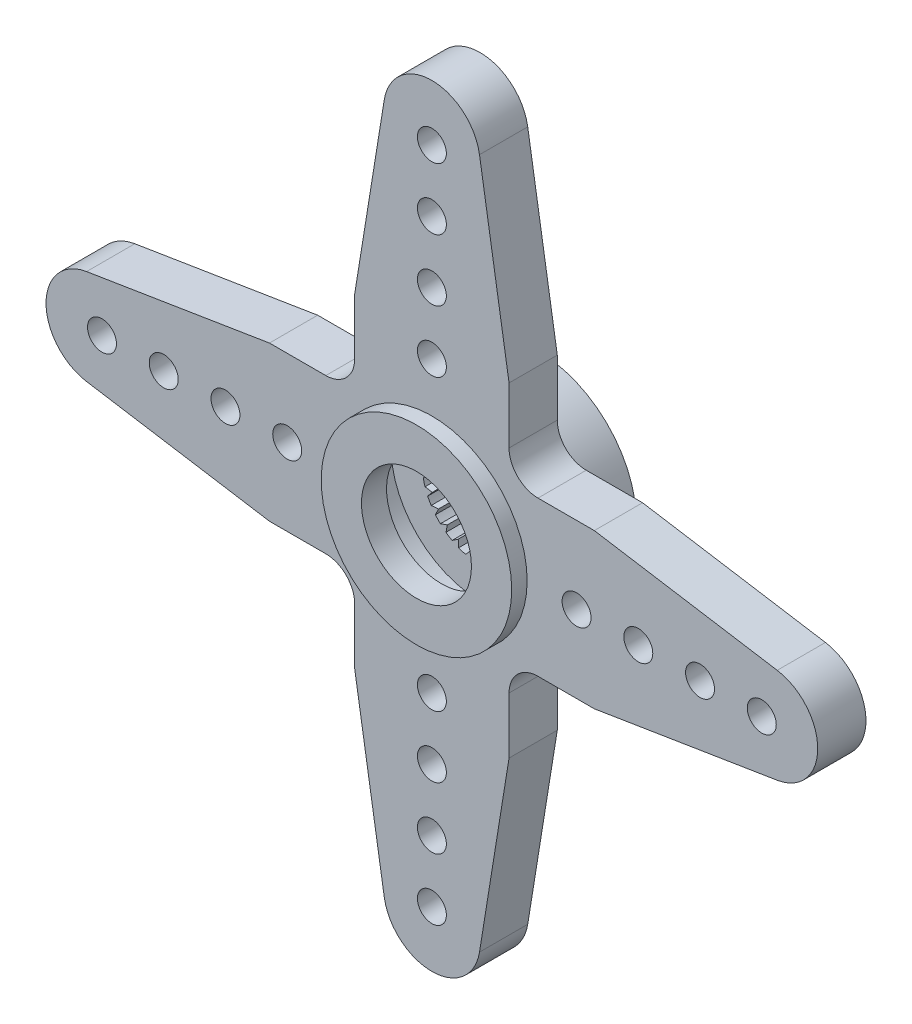
SolidWorks part; units mm, degrees
ref_plane "Front Plane" through (0, 0, 0) normal (0, 0, 1) x (1, 0, 0)
ref_plane "Top Plane" through (0, 0, 0) normal (0, 1, 0) x (1, 0, 0)
ref_plane "Right Plane" through (0, 0, 0) normal (1, 0, 0) x (0, 0, -1)
ref_plane "Plane1" through (0, 0, 2.5) normal (0, 0, 1) x (1, 0, 0)
sketch "Sketch1" plane through (0, 0, 2.5) normal (0, 0, 1) x (1, 0, 0)
  line L0 (4, -8.4192) -> (4, -4)
  line L1 (4, -4) -> (8.4192, -4)
  line L2 (8.4192, -4) -> (17.8989, -2.468)
  line L3 (17.8989, 2.468) -> (8.4192, 4)
  line L4 (8.4192, 4) -> (4, 4)
  line L5 (4, 4) -> (4, 8.4192)
  line L6 (4, 8.4192) -> (2.468, 17.8989)
  line L7 (-2.468, 17.8989) -> (-4, 8.4192)
  line L8 (-4, 8.4192) -> (-4, 4)
  line L9 (-4, 4) -> (-8.4192, 4)
  line L10 (-8.4192, 4) -> (-17.8989, 2.468)
  line L11 (-17.8989, -2.468) -> (-8.4192, -4)
  line L12 (-8.4192, -4) -> (-4, -4)
  line L13 (-4, -4) -> (-4, -8.4192)
  line L14 (-4, -8.4192) -> (-2.468, -17.8989)
  line L15 (2.468, -17.8989) -> (4, -8.4192)
  arc A0 (17.8989, -2.468) -> (17.8989, 2.468) centre (17.5, 0) ccw
  arc A1 (2.468, 17.8989) -> (-2.468, 17.8989) centre (0, 17.5) ccw
  arc A2 (-17.8989, 2.468) -> (-17.8989, -2.468) centre (-17.5, 0) ccw
  arc A3 (-2.468, -17.8989) -> (2.468, -17.8989) centre (0, -17.5) ccw
extrude "Boss-Extrude1" add sketch "Sketch1" against normal blind 2.5
hole_wizard "M8 Clearance Hole1" positions "Sketch3" profile "Sketch2" hole size "M8" standard "ANSI Metric"
sketch "Sketch3" plane through (0, 0, 2.5) normal (0, 0, 1) x (1, 0, 0)
  point P0 (0, 0)
sketch "Sketch2" plane through (0, 0, 2.5) normal (1, 0, 0) x (0, -1, 0)
  line L0 (0, 0) -> (0, 2.5)
  line L1 (0, 2.5) -> (4.625, 2.5)
  line L2 (4.625, 2.5) -> (4.625, 0)
  line L5 (4.625, 0) -> (0, 0)
  line L11 (0, -6.35) -> (0, 107.95) construction
  dimension "Thru Hole Dia." = 9.25
  dimension "Thru Hole Depth" = 2.5
ref_plane "Plane2" through (0, 0, 2) normal (0, 0, -1) x (-1, 0, 0)
sketch "Sketch4" plane through (0, 0, 2) normal (0, 0, -1) x (-1, 0, 0)
  circle A0 centre (0, 0) radius 4.938
extrude "Boss-Extrude2" add sketch "Sketch4" against normal blind 1.3
sketch "Sketch5" plane through (0, 0, 0) normal (0, 0, 1) x (1, 0, 0)
  circle A0 centre (0, 0) radius 5.0996
extrude "Boss-Extrude3" add sketch "Sketch5" against normal blind 3
sketch "Sketch6" plane through (0, 0, -3) normal (0, 0, -1) x (-1, 0, 0)
  line L0 (-2.9946, 0.1807) -> (-2.6675, 0)
  line L1 (-2.6675, 0) -> (-2.9936, -0.1964)
  line L2 (-2.9454, -0.5697) -> (-2.5837, -0.6634)
  line L3 (-2.5837, -0.6634) -> (-2.8507, -0.9347)
  line L4 (-2.7112, -1.2843) -> (-2.3375, -1.2851)
  line L5 (-2.3375, -1.2851) -> (-2.5287, -1.6143)
  line L6 (-2.3066, -1.9182) -> (-1.9445, -1.826)
  line L7 (-1.9445, -1.826) -> (-2.0478, -2.1924)
  line L8 (-1.7571, -2.4316) -> (-1.4293, -2.2522)
  line L9 (-1.4293, -2.2522) -> (-1.4382, -2.6328)
  line L10 (-1.0972, -2.7922) -> (-0.8243, -2.5369)
  line L11 (-0.8243, -2.5369) -> (-0.7383, -2.9077)
  line L12 (-0.3683, -2.9773) -> (-0.1675, -2.6622)
  line L13 (-0.1675, -2.6622) -> (0.0081, -3)
  line L14 (0.3837, -2.9754) -> (0.4998, -2.6202)
  line L15 (0.4998, -2.6202) -> (0.7539, -2.9037)
  line L16 (1.1115, -2.7865) -> (1.1358, -2.4136)
  line L17 (1.1358, -2.4136) -> (1.4523, -2.625)
  line L18 (1.7696, -2.4225) -> (1.7003, -2.0553)
  line L19 (1.7003, -2.0553) -> (2.0595, -2.1814)
  line L20 (2.3164, -1.9063) -> (2.158, -1.5679)
  line L21 (2.158, -1.5679) -> (2.5373, -1.6007)
  line L22 (2.7178, -1.2704) -> (2.4802, -0.982)
  line L23 (2.4802, -0.982) -> (2.8556, -0.9194)
  line L24 (2.9483, -0.5546) -> (2.6464, -0.3343)
  line L25 (2.6464, -0.3343) -> (2.9946, -0.1803)
  line L26 (2.9936, 0.1961) -> (2.6464, 0.3343)
  line L27 (2.6464, 0.3343) -> (2.9453, 0.5701)
  line L28 (2.8508, 0.9344) -> (2.4802, 0.982)
  line L29 (2.4802, 0.982) -> (2.711, 1.2846)
  line L30 (2.5288, 1.614) -> (2.158, 1.5679)
  line L31 (2.158, 1.5679) -> (2.3064, 1.9185)
  line L32 (2.048, 2.1922) -> (1.7003, 2.0553)
  line L33 (1.7003, 2.0553) -> (1.7568, 2.4318)
  line L34 (1.4385, 2.6326) -> (1.1358, 2.4136)
  line L35 (1.1358, 2.4136) -> (1.0969, 2.7923)
  line L36 (0.7386, 2.9077) -> (0.4998, 2.6202)
  line L37 (0.4998, 2.6202) -> (0.368, 2.9773)
  line L38 (-0.0077, 3) -> (-0.1675, 2.6622)
  line L39 (-0.1675, 2.6622) -> (-0.384, 2.9753)
  line L40 (-0.7535, 2.9038) -> (-0.8243, 2.5369)
  line L41 (-0.8243, 2.5369) -> (-1.1119, 2.7864)
  line L42 (-1.452, 2.6252) -> (-1.4293, 2.2522)
  line L43 (-1.4293, 2.2522) -> (-1.7699, 2.4223)
  line L44 (-2.0593, 2.1816) -> (-1.9445, 1.826)
  line L45 (-1.9445, 1.826) -> (-2.3167, 1.9061)
  line L46 (-2.5371, 1.601) -> (-2.3375, 1.2851)
  line L47 (-2.3375, 1.2851) -> (-2.7179, 1.27)
  line L48 (-2.8555, 0.9197) -> (-2.5837, 0.6634)
  line L49 (-2.5837, 0.6634) -> (-2.9484, 0.5542)
  arc A0 (-2.9936, -0.1964) -> (-2.9454, -0.5697) centre (0, 0) ccw
  arc A1 (-2.8507, -0.9347) -> (-2.7112, -1.2843) centre (0, 0) ccw
  arc A2 (-2.5287, -1.6143) -> (-2.3066, -1.9182) centre (0, 0) ccw
  arc A3 (-2.0478, -2.1924) -> (-1.7571, -2.4316) centre (0, 0) ccw
  arc A4 (-1.4382, -2.6328) -> (-1.0972, -2.7922) centre (0, 0) ccw
  arc A5 (-0.7383, -2.9077) -> (-0.3683, -2.9773) centre (0, 0) ccw
  arc A6 (0.0081, -3) -> (0.3837, -2.9754) centre (0, 0) ccw
  arc A7 (0.7539, -2.9037) -> (1.1115, -2.7865) centre (0, 0) ccw
  arc A8 (1.4523, -2.625) -> (1.7696, -2.4225) centre (0, 0) ccw
  arc A9 (2.0595, -2.1814) -> (2.3164, -1.9063) centre (0, 0) ccw
  arc A10 (2.5373, -1.6007) -> (2.7178, -1.2704) centre (0, 0) ccw
  arc A11 (2.8556, -0.9194) -> (2.9483, -0.5546) centre (0, 0) ccw
  arc A12 (2.9946, -0.1803) -> (2.9936, 0.1961) centre (0, 0) ccw
  arc A13 (2.9453, 0.5701) -> (2.8508, 0.9344) centre (0, 0) ccw
  arc A14 (2.711, 1.2846) -> (2.5288, 1.614) centre (0, 0) ccw
  arc A15 (2.3064, 1.9185) -> (2.048, 2.1922) centre (0, 0) ccw
  arc A16 (1.7568, 2.4318) -> (1.4385, 2.6326) centre (0, 0) ccw
  arc A17 (1.0969, 2.7923) -> (0.7386, 2.9077) centre (0, 0) ccw
  arc A18 (0.368, 2.9773) -> (-0.0077, 3) centre (0, 0) ccw
  arc A19 (-0.384, 2.9753) -> (-0.7535, 2.9038) centre (0, 0) ccw
  arc A20 (-1.1119, 2.7864) -> (-1.452, 2.6252) centre (0, 0) ccw
  arc A21 (-1.7699, 2.4223) -> (-2.0593, 2.1816) centre (0, 0) ccw
  arc A22 (-2.3167, 1.9061) -> (-2.5371, 1.601) centre (0, 0) ccw
  arc A23 (-2.7179, 1.27) -> (-2.8555, 0.9197) centre (0, 0) ccw
  arc A24 (-2.9484, 0.5542) -> (-2.9946, 0.1807) centre (0, 0) ccw
extrude "Cut-Extrude1" cut sketch "Sketch6" against normal blind 3.6
hole_wizard "Ø1.5 (1.5) Diameter Hole1" positions "Sketch8" profile "Sketch7" hole size "Ø1.5" standard "ANSI Metric"
sketch "Sketch8" plane through (0, 0, 0) normal (0, 0, -1) x (-1, 0, 0)
  point P0 (0, 17.1)
  point P1 (0, 13.9)
  point P2 (0, 10.7)
  point P3 (0, 7.5)
  point P4 (17.1, 0)
  point P5 (13.9, 0)
  point P6 (10.7, 0)
  point P7 (7.5, 0)
  point P8 (-17.1, 0)
  point P9 (-13.9, 0)
  point P10 (-10.7, 0)
  point P11 (-7.5, 0)
  point P12 (0, -17.1)
  point P13 (0, -13.9)
  point P14 (0, -10.7)
  point P15 (0, -7.5)
sketch "Sketch7" plane through (0, 17.1, 0) normal (1, 0, 0) x (0, 1, 0)
  line L0 (0, 0) -> (0, 2.5)
  line L1 (0, 2.5) -> (0.75, 2.5)
  line L2 (0.75, 2.5) -> (0.75, 0)
  line L5 (0.75, 0) -> (0, 0)
  line L11 (0, -6.35) -> (0, 107.95) construction
  dimension "Thru Hole Dia." = 1.5
  dimension "Thru Hole Depth" = 2.5
hole_wizard "CBORE for M2.5 Hex Head Machine Screw1" positions "Sketch10" profile "Sketch9" counterbore size "M2.5" standard "ANSI Metric"
sketch "Sketch10" plane through (0, 0, 3.3) normal (0, 0, 1) x (1, 0, 0)
  point P0 (0, 0)
sketch "Sketch9" plane through (0, 0, 3.3) normal (1, 0, 0) x (0, -1, 0)
  line L0 (0, 0) -> (0, 1.3)
  line L1 (0, 1.3) -> (1.5, 1.3)
  line L3 (1.5, 1.3) -> (1.5, 1.5)
  line L4 (1.5, 1.5) -> (2.85, 1.5)
  line L5 (2.85, 1.5) -> (2.85, 0)
  line L7 (2.85, 0) -> (0, 0)
  line L11 (0, -6.35) -> (0, 107.95) construction
  dimension "Thru Hole Dia." = 3
  dimension "Thru Hole Depth" = 1.3
  dimension "C'Bore Dia." = 5.7
  dimension "C'Bore Depth" = 1.5
ref_plane "Plane3" through (0, 0, 0) normal (0.7071, 0.7071, 0) x (-0.7071, 0.7071, 0)
ref_plane "Plane4" through (0, 0, 0) normal (-0.7071, -0.7071, 0) x (0.7071, -0.7071, 0)
ref_plane "Plane5" through (0, 0, 0) normal (-0.7071, 0.7071, 0) x (-0.7071, -0.7071, 0)
ref_plane "Plane6" through (0, 0, 0) normal (0.7071, -0.7071, 0) x (0.7071, 0.7071, 0)
ref_plane "Plane7" through (0, 0, 0) normal (-1, 0, 0) x (0, -1, 0)
ref_plane "Plane8" through (0, 0, 0) normal (0, -1, 0) x (1, 0, 0)
fillet "Fillet1" radius 1.5 4 edges at (4, -4, 1.25) (-4, -4, 1.25) (-4, 4, 1.25) (4, 4, 1.25) tangent propagation no
